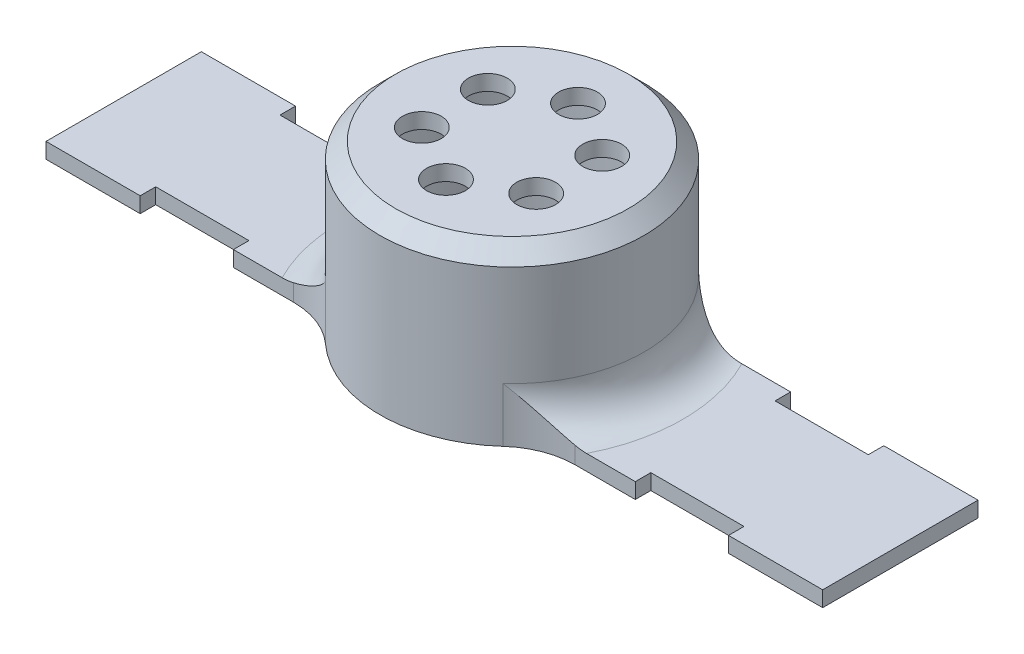
SolidWorks part; units mm, degrees
ref_plane "前视基准面" through (0, 0, 0) normal (0, 0, 1) x (1, 0, 0)
ref_plane "上视基准面" through (0, 0, 0) normal (0, 1, 0) x (1, 0, 0)
ref_plane "右视基准面" through (0, 0, 0) normal (1, 0, 0) x (0, 0, -1)
sketch "草图1" plane through (0, 0, 0) normal (0, 1, 0) x (1, 0, 0)
  line L1 (-50, 10) -> (50, 10)
  line L2 (-50, 10) -> (-50, -10)
  line L3 (-50, -10) -> (50, -10)
  line L4 (50, 10) -> (50, -10)
  line L5 (-50, 10) -> (50, -10) construction
  line L6 (-50, -10) -> (50, 10) construction
  point P0 (0, 0)
  dimension "D1" = 50
  dimension "D2" = 20
extrude "凸台-拉伸1" add sketch "草图1" along normal blind 2
sketch "草图2" plane through (0, 0, 0) normal (0, 1, 0) x (1, 0, 0)
  circle A0 centre (0, 0) radius 17
  dimension "D1" = 34
extrude "凸台-拉伸2" add sketch "草图2" along normal blind 22
sketch "草图3" plane through (0, 0, 0) normal (0, 1, 0) x (1, 0, 0)
  circle A0 centre (0, 0) radius 15
  dimension "D1" = 30
extrude "切除-拉伸1" cut sketch "草图3" along normal offset from surface (20 mm away) 2 up to face at (0, 22, 17)
sketch "草图4" plane through (0, 0, 0) normal (0, 1, 0) x (1, 0, 0)
  line L0 (-31.8739, -10) -> (-31.8739, 10) construction
  line L1 (-50, -10) -> (-13.7477, -10) construction
  line L2 (-13.7477, 10) -> (-50, 10) construction
  line L4 (-25.8739, -8) -> (-37.8739, -8)
  line L5 (-25.8739, -8) -> (-25.8739, -10)
  line L6 (-25.8739, -10) -> (-37.8739, -10)
  line L7 (-37.8739, -8) -> (-37.8739, -10)
  line L8 (-25.8739, -8) -> (-37.8739, -10) construction
  line L9 (-25.8739, -10) -> (-37.8739, -8) construction
  point P6 (-31.8739, -9)
  dimension "D1" = 2
  dimension "D2" = 12
extrude "切除-拉伸3" cut sketch "草图4" along normal up to next
mirror "镜向1" about plane through (0, 0, 0) normal (0, 0, 1) of "切除-拉伸3"
mirror "镜向2" about plane through (0, 0, 0) normal (1, 0, 0) of "镜向1"
fillet "圆角1" radius 10 4 edges at (-13.7477, 1, -10) (13.7477, 1, -10) (13.7477, 1, 10) (-13.7477, 1, 10)
fillet "圆角2" radius 5 2 edges at (17, 2, 0) (-17, 2, 0)
chamfer "倒角1" distance 2 angle 45 2 edges at (0, 20, 15) (0, 22, 17)
sketch "草图5" plane through (0, 20, 0) normal (0, -1, 0) x (1, 0, 0)
  circle A0 centre (0, 0) radius 8.5 construction
  circle A1 centre (0, 8.5) radius 2.5
  circle A2 centre (7.3612, 4.25) radius 2.5
  circle A3 centre (7.3612, -4.25) radius 2.5
  circle A4 centre (0, -8.5) radius 2.5
  circle A5 centre (-7.3612, -4.25) radius 2.5
  circle A6 centre (-7.3612, 4.25) radius 2.5
  point P5 (-3.4312, -9.3993)
  point P6 (0, 0)
  point P18 (0, 0)
  dimension "D1" = 5
  dimension "D2" = 17
  dimension "D3" = 6
extrude "切除-拉伸4" cut sketch "草图5" against normal up to next
equation "\"拨盘中径\"= 64'8ball"
equation "\"球通道直径\"= 18"
equation "\"壁厚\"=2"
equation "\"加强筋高\"= 4"
equation "\"M3螺丝孔\"= 3.2"
equation "\"M3沉头孔\"= 6.5'杯头螺钉头高3mm"
equation "\"M3螺母孔\"= 6"
equation "\"电机杯直径\"= 30"
equation "\"线槽宽\"= 16"
equation "\"线槽高\"= 8"
equation "\"D2@草图1\"=\"线槽宽\"+\"壁厚\"*2"
equation "\"D1@凸台-拉伸1\"=\"壁厚\""
equation "\"D1@草图2\"=\"电机杯直径\"+\"壁厚\"*2"
equation "\"D1@凸台-拉伸2\"=20 + \"壁厚\""
equation "\"D1@草图3\"=\"电机杯直径\""
equation "\"D1@切除-拉伸1\"=\"壁厚\""
equation "\"D1@草图4\"=\"壁厚\""
